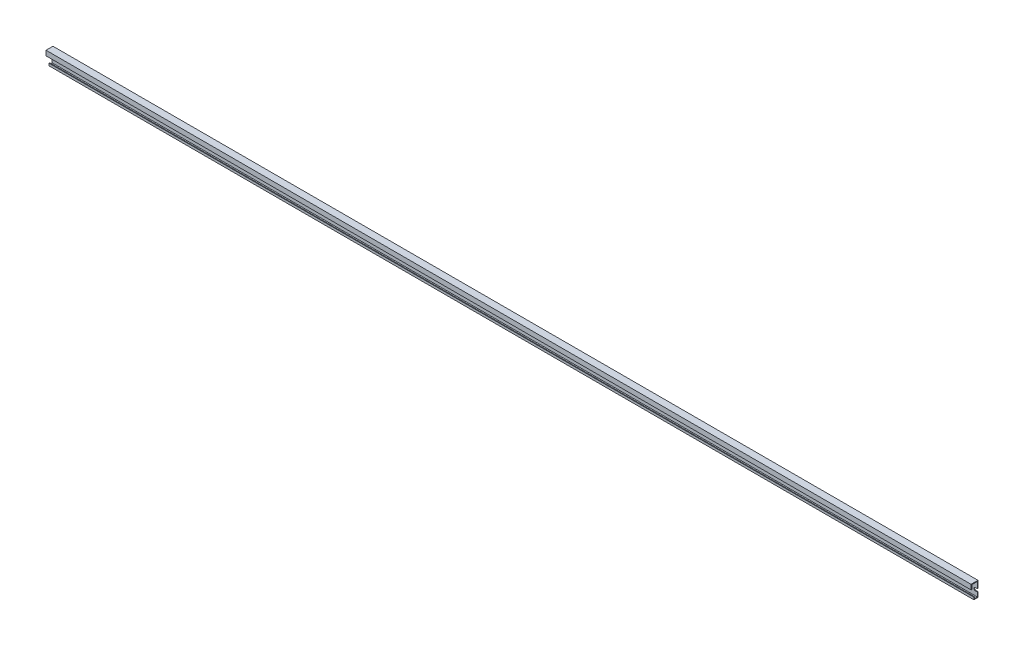
SolidWorks part; units mm, degrees
ref_plane "Front Plane" through (0, 0, 0) normal (0, 0, 1) x (1, 0, 0)
ref_plane "Top Plane" through (0, 0, 0) normal (0, 1, 0) x (1, 0, 0)
ref_plane "Right Plane" through (0, 0, 0) normal (1, 0, 0) x (0, 0, -1)
ref_plane "Plane1" through (0, -11, 0) normal (0, 1, 0) x (1, 0, 0)
sketch "Sketch1" plane through (0, -11, 0) normal (0, 1, 0) x (1, 0, 0)
  line L0 (2000, -9) -> (2000, 0)
  line L1 (2000, 0) -> (0, 0)
  line L2 (0, 0) -> (0, -9)
  line L3 (0, -9) -> (2000, -9)
extrude "Boss-Extrude1" add sketch "Sketch1" against normal blind 5
sketch "Sketch2" plane through (0, 0, 0) normal (-1, 0, 0) x (0, 0, 1)
  line L0 (0, -14.5) -> (7.5, -14.5)
  line L1 (7.5, -14.5) -> (7.5, -11)
  line L2 (7.5, -11) -> (0, -11)
  line L3 (0, -11) -> (0, -14.5)
extrude "Cut-Extrude1" cut sketch "Sketch2" against normal through all
sketch "Sketch3" plane through (0, -14.5, 0) normal (0, 1, 0) x (-1, 0, 0)
  line L0 (0, 1.5) -> (0, 0)
  line L1 (0, 0) -> (-2000, 0)
  line L2 (-2000, 0) -> (-2000, 1.5)
  line L3 (-2000, 1.5) -> (0, 1.5)
extrude "Boss-Extrude2" add sketch "Sketch3" along normal blind 30.5
sketch "Sketch4" plane through (0, 0, 1.5) normal (0, 0, 1) x (1, 0, 0)
  line L0 (0, 14.5) -> (0, 16)
  line L1 (0, 16) -> (2000, 16)
  line L2 (2000, 16) -> (2000, 14.5)
  line L3 (2000, 14.5) -> (0, 14.5)
extrude "Boss-Extrude3" add sketch "Sketch4" along normal blind 13.5
sketch "Sketch5" plane through (0, 14.5, 0) normal (0, -1, 0) x (1, 0, 0)
  line L0 (2000, 15) -> (2000, 13.5)
  line L1 (2000, 13.5) -> (0, 13.5)
  line L2 (0, 13.5) -> (0, 15)
  line L3 (0, 15) -> (2000, 15)
extrude "Boss-Extrude4" add sketch "Sketch5" along normal blind 9
sketch "Sketch6" plane through (0, 0, 0) normal (0, 0, -1) x (-1, 0, 0)
  line L0 (0, -5.1) -> (0, 1.1)
  line L1 (0, 1.1) -> (-4.4, 1.1)
  line L2 (-4.4, -5.1) -> (0, -5.1)
  arc A0 (-4.4, 1.1) -> (-4.4, -5.1) centre (-4.4, -2) ccw
extrude "Cut-Extrude2" cut sketch "Sketch6" against normal through all
sketch "Sketch7" plane through (0, 0, 0) normal (0, 0, -1) x (-1, 0, 0)
  line L0 (-2000, 1.1) -> (-2000, -5.1)
  line L1 (-2000, -5.1) -> (-1995.6, -5.1)
  line L2 (-1995.6, 1.1) -> (-2000, 1.1)
  arc A0 (-1995.6, -5.1) -> (-1995.6, 1.1) centre (-1995.6, -2) ccw
extrude "Cut-Extrude3" cut sketch "Sketch7" against normal through all
sketch "Sketch8" plane through (0, 0, 1.5) normal (0, 0, 1) x (1, 0, 0)
  line L0 (1229.4, 1.1) -> (1220.6, 1.1)
  line L1 (1220.6, -5.1) -> (1229.4, -5.1)
  arc A0 (1220.6, 1.1) -> (1220.6, -5.1) centre (1220.6, -2) ccw
  arc A1 (1229.4, -5.1) -> (1229.4, 1.1) centre (1229.4, -2) ccw
extrude "Cut-Extrude4" cut sketch "Sketch8" against normal through all
sketch "Sketch9" plane through (0, 0, 1.5) normal (0, 0, 1) x (1, 0, 0)
  line L0 (279.4, 1.1) -> (270.6, 1.1)
  line L1 (270.6, -5.1) -> (279.4, -5.1)
  arc A0 (270.6, 1.1) -> (270.6, -5.1) centre (270.6, -2) ccw
  arc A1 (279.4, -5.1) -> (279.4, 1.1) centre (279.4, -2) ccw
extrude "Cut-Extrude5" cut sketch "Sketch9" against normal through all
sketch "Sketch10" plane through (0, 0, 1.5) normal (0, 0, 1) x (1, 0, 0)
  line L0 (1404.4, 1.1) -> (1395.6, 1.1)
  line L1 (1395.6, -5.1) -> (1404.4, -5.1)
  arc A0 (1395.6, 1.1) -> (1395.6, -5.1) centre (1395.6, -2) ccw
  arc A1 (1404.4, -5.1) -> (1404.4, 1.1) centre (1404.4, -2) ccw
extrude "Cut-Extrude6" cut sketch "Sketch10" against normal through all
sketch "Sketch11" plane through (0, 0, 1.5) normal (0, 0, 1) x (1, 0, 0)
  line L0 (1729.4, 1.1) -> (1720.6, 1.1)
  line L1 (1720.6, -5.1) -> (1729.4, -5.1)
  arc A0 (1729.4, -5.1) -> (1729.4, 1.1) centre (1729.4, -2) ccw
  arc A1 (1720.6, 1.1) -> (1720.6, -5.1) centre (1720.6, -2) ccw
extrude "Cut-Extrude7" cut sketch "Sketch11" against normal through all
sketch "Sketch12" plane through (0, 0, 1.5) normal (0, 0, 1) x (1, 0, 0)
  line L0 (1954.4, 1.1) -> (1945.6, 1.1)
  line L1 (1945.6, -5.1) -> (1954.4, -5.1)
  arc A0 (1954.4, -5.1) -> (1954.4, 1.1) centre (1954.4, -2) ccw
  arc A1 (1945.6, 1.1) -> (1945.6, -5.1) centre (1945.6, -2) ccw
extrude "Cut-Extrude8" cut sketch "Sketch12" against normal through all
sketch "Sketch13" plane through (0, 0, 1.5) normal (0, 0, 1) x (1, 0, 0)
  line L0 (679.4, 1.1) -> (670.6, 1.1)
  line L1 (670.6, -5.1) -> (679.4, -5.1)
  arc A0 (670.6, 1.1) -> (670.6, -5.1) centre (670.6, -2) ccw
  arc A1 (679.4, -5.1) -> (679.4, 1.1) centre (679.4, -2) ccw
extrude "Cut-Extrude9" cut sketch "Sketch13" against normal through all
sketch "Sketch14" plane through (0, 0, 1.5) normal (0, 0, 1) x (1, 0, 0)
  line L0 (29.4, 1.1) -> (20.6, 1.1)
  line L1 (20.6, -5.1) -> (29.4, -5.1)
  arc A0 (20.6, 1.1) -> (20.6, -5.1) centre (20.6, -2) ccw
  arc A1 (29.4, -5.1) -> (29.4, 1.1) centre (29.4, -2) ccw
extrude "Cut-Extrude10" cut sketch "Sketch14" against normal through all
sketch "Sketch15" plane through (0, 0, 1.5) normal (0, 0, 1) x (1, 0, 0)
  line L0 (1979.4, 1.1) -> (1970.6, 1.1)
  line L1 (1970.6, -5.1) -> (1979.4, -5.1)
  arc A0 (1979.4, -5.1) -> (1979.4, 1.1) centre (1979.4, -2) ccw
  arc A1 (1970.6, 1.1) -> (1970.6, -5.1) centre (1970.6, -2) ccw
extrude "Cut-Extrude11" cut sketch "Sketch15" against normal through all
sketch "Sketch16" plane through (0, 0, 1.5) normal (0, 0, 1) x (1, 0, 0)
  line L0 (104.4, 1.1) -> (95.6, 1.1)
  line L1 (95.6, -5.1) -> (104.4, -5.1)
  arc A0 (95.6, 1.1) -> (95.6, -5.1) centre (95.6, -2) ccw
  arc A1 (104.4, -5.1) -> (104.4, 1.1) centre (104.4, -2) ccw
extrude "Cut-Extrude12" cut sketch "Sketch16" against normal through all
sketch "Sketch17" plane through (0, 0, 1.5) normal (0, 0, 1) x (1, 0, 0)
  line L0 (1479.4, 1.1) -> (1470.6, 1.1)
  line L1 (1470.6, -5.1) -> (1479.4, -5.1)
  arc A0 (1479.4, -5.1) -> (1479.4, 1.1) centre (1479.4, -2) ccw
  arc A1 (1470.6, 1.1) -> (1470.6, -5.1) centre (1470.6, -2) ccw
extrude "Cut-Extrude13" cut sketch "Sketch17" against normal through all
sketch "Sketch18" plane through (0, 0, 1.5) normal (0, 0, 1) x (1, 0, 0)
  line L0 (295.6, -5.1) -> (304.4, -5.1)
  line L1 (304.4, 1.1) -> (295.6, 1.1)
  arc A0 (304.4, -5.1) -> (304.4, 1.1) centre (304.4, -2) ccw
  arc A1 (295.6, 1.1) -> (295.6, -5.1) centre (295.6, -2) ccw
extrude "Cut-Extrude14" cut sketch "Sketch18" against normal through all
sketch "Sketch19" plane through (0, 0, 1.5) normal (0, 0, 1) x (1, 0, 0)
  line L0 (170.6, -5.1) -> (179.4, -5.1)
  line L1 (179.4, 1.1) -> (170.6, 1.1)
  arc A0 (179.4, -5.1) -> (179.4, 1.1) centre (179.4, -2) ccw
  arc A1 (170.6, 1.1) -> (170.6, -5.1) centre (170.6, -2) ccw
extrude "Cut-Extrude15" cut sketch "Sketch19" against normal through all
sketch "Sketch20" plane through (0, 0, 1.5) normal (0, 0, 1) x (1, 0, 0)
  line L0 (1320.6, -5.1) -> (1329.4, -5.1)
  line L1 (1329.4, 1.1) -> (1320.6, 1.1)
  arc A0 (1329.4, -5.1) -> (1329.4, 1.1) centre (1329.4, -2) ccw
  arc A1 (1320.6, 1.1) -> (1320.6, -5.1) centre (1320.6, -2) ccw
extrude "Cut-Extrude16" cut sketch "Sketch20" against normal through all
sketch "Sketch21" plane through (0, 0, 1.5) normal (0, 0, 1) x (1, 0, 0)
  line L0 (704.4, 1.1) -> (695.6, 1.1)
  line L1 (695.6, -5.1) -> (704.4, -5.1)
  arc A0 (695.6, 1.1) -> (695.6, -5.1) centre (695.6, -2) ccw
  arc A1 (704.4, -5.1) -> (704.4, 1.1) centre (704.4, -2) ccw
extrude "Cut-Extrude17" cut sketch "Sketch21" against normal through all
sketch "Sketch22" plane through (0, 0, 1.5) normal (0, 0, 1) x (1, 0, 0)
  line L0 (379.4, 1.1) -> (370.6, 1.1)
  line L1 (370.6, -5.1) -> (379.4, -5.1)
  arc A0 (370.6, 1.1) -> (370.6, -5.1) centre (370.6, -2) ccw
  arc A1 (379.4, -5.1) -> (379.4, 1.1) centre (379.4, -2) ccw
extrude "Cut-Extrude18" cut sketch "Sketch22" against normal through all
sketch "Sketch23" plane through (0, 0, 1.5) normal (0, 0, 1) x (1, 0, 0)
  line L0 (1554.4, 1.1) -> (1545.6, 1.1)
  line L1 (1545.6, -5.1) -> (1554.4, -5.1)
  arc A0 (1554.4, -5.1) -> (1554.4, 1.1) centre (1554.4, -2) ccw
  arc A1 (1545.6, 1.1) -> (1545.6, -5.1) centre (1545.6, -2) ccw
extrude "Cut-Extrude19" cut sketch "Sketch23" against normal through all
sketch "Sketch24" plane through (0, 0, 1.5) normal (0, 0, 1) x (1, 0, 0)
  line L0 (1704.4, 1.1) -> (1695.6, 1.1)
  line L1 (1695.6, -5.1) -> (1704.4, -5.1)
  arc A0 (1695.6, 1.1) -> (1695.6, -5.1) centre (1695.6, -2) ccw
  arc A1 (1704.4, -5.1) -> (1704.4, 1.1) centre (1704.4, -2) ccw
extrude "Cut-Extrude20" cut sketch "Sketch24" against normal through all
sketch "Sketch25" plane through (0, 0, 1.5) normal (0, 0, 1) x (1, 0, 0)
  line L0 (1004.4, 1.1) -> (995.6, 1.1)
  line L1 (995.6, -5.1) -> (1004.4, -5.1)
  arc A0 (995.6, 1.1) -> (995.6, -5.1) centre (995.6, -2) ccw
  arc A1 (1004.4, -5.1) -> (1004.4, 1.1) centre (1004.4, -2) ccw
extrude "Cut-Extrude21" cut sketch "Sketch25" against normal through all
sketch "Sketch26" plane through (0, 0, 1.5) normal (0, 0, 1) x (1, 0, 0)
  line L0 (545.6, -5.1) -> (554.4, -5.1)
  line L1 (554.4, 1.1) -> (545.6, 1.1)
  arc A0 (554.4, -5.1) -> (554.4, 1.1) centre (554.4, -2) ccw
  arc A1 (545.6, 1.1) -> (545.6, -5.1) centre (545.6, -2) ccw
extrude "Cut-Extrude22" cut sketch "Sketch26" against normal through all
sketch "Sketch27" plane through (0, 0, 1.5) normal (0, 0, 1) x (1, 0, 0)
  line L0 (845.6, -5.1) -> (854.4, -5.1)
  line L1 (854.4, 1.1) -> (845.6, 1.1)
  arc A0 (854.4, -5.1) -> (854.4, 1.1) centre (854.4, -2) ccw
  arc A1 (845.6, 1.1) -> (845.6, -5.1) centre (845.6, -2) ccw
extrude "Cut-Extrude23" cut sketch "Sketch27" against normal through all
sketch "Sketch28" plane through (0, 0, 1.5) normal (0, 0, 1) x (1, 0, 0)
  line L0 (879.4, 1.1) -> (870.6, 1.1)
  line L1 (870.6, -5.1) -> (879.4, -5.1)
  arc A0 (870.6, 1.1) -> (870.6, -5.1) centre (870.6, -2) ccw
  arc A1 (879.4, -5.1) -> (879.4, 1.1) centre (879.4, -2) ccw
extrude "Cut-Extrude24" cut sketch "Sketch28" against normal through all
sketch "Sketch29" plane through (0, 0, 1.5) normal (0, 0, 1) x (1, 0, 0)
  line L0 (354.4, 1.1) -> (345.6, 1.1)
  line L1 (345.6, -5.1) -> (354.4, -5.1)
  arc A0 (345.6, 1.1) -> (345.6, -5.1) centre (345.6, -2) ccw
  arc A1 (354.4, -5.1) -> (354.4, 1.1) centre (354.4, -2) ccw
extrude "Cut-Extrude25" cut sketch "Sketch29" against normal through all
sketch "Sketch30" plane through (0, 0, 1.5) normal (0, 0, 1) x (1, 0, 0)
  line L0 (1679.4, 1.1) -> (1670.6, 1.1)
  line L1 (1670.6, -5.1) -> (1679.4, -5.1)
  arc A0 (1670.6, 1.1) -> (1670.6, -5.1) centre (1670.6, -2) ccw
  arc A1 (1679.4, -5.1) -> (1679.4, 1.1) centre (1679.4, -2) ccw
extrude "Cut-Extrude26" cut sketch "Sketch30" against normal through all
sketch "Sketch31" plane through (0, 0, 1.5) normal (0, 0, 1) x (1, 0, 0)
  line L0 (395.6, -5.1) -> (404.4, -5.1)
  line L1 (404.4, 1.1) -> (395.6, 1.1)
  arc A0 (404.4, -5.1) -> (404.4, 1.1) centre (404.4, -2) ccw
  arc A1 (395.6, 1.1) -> (395.6, -5.1) centre (395.6, -2) ccw
extrude "Cut-Extrude27" cut sketch "Sketch31" against normal through all
sketch "Sketch32" plane through (0, 0, 1.5) normal (0, 0, 1) x (1, 0, 0)
  line L0 (1454.4, 1.1) -> (1445.6, 1.1)
  line L1 (1445.6, -5.1) -> (1454.4, -5.1)
  arc A0 (1445.6, 1.1) -> (1445.6, -5.1) centre (1445.6, -2) ccw
  arc A1 (1454.4, -5.1) -> (1454.4, 1.1) centre (1454.4, -2) ccw
extrude "Cut-Extrude28" cut sketch "Sketch32" against normal through all
sketch "Sketch33" plane through (0, 0, 1.5) normal (0, 0, 1) x (1, 0, 0)
  line L0 (54.4, 1.1) -> (45.6, 1.1)
  line L1 (45.6, -5.1) -> (54.4, -5.1)
  arc A0 (45.6, 1.1) -> (45.6, -5.1) centre (45.6, -2) ccw
  arc A1 (54.4, -5.1) -> (54.4, 1.1) centre (54.4, -2) ccw
extrude "Cut-Extrude29" cut sketch "Sketch33" against normal through all
sketch "Sketch34" plane through (0, 0, 1.5) normal (0, 0, 1) x (1, 0, 0)
  line L0 (1604.4, 1.1) -> (1595.6, 1.1)
  line L1 (1595.6, -5.1) -> (1604.4, -5.1)
  arc A0 (1595.6, 1.1) -> (1595.6, -5.1) centre (1595.6, -2) ccw
  arc A1 (1604.4, -5.1) -> (1604.4, 1.1) centre (1604.4, -2) ccw
extrude "Cut-Extrude30" cut sketch "Sketch34" against normal through all
sketch "Sketch35" plane through (0, 0, 1.5) normal (0, 0, 1) x (1, 0, 0)
  line L0 (1929.4, 1.1) -> (1920.6, 1.1)
  line L1 (1920.6, -5.1) -> (1929.4, -5.1)
  arc A0 (1920.6, 1.1) -> (1920.6, -5.1) centre (1920.6, -2) ccw
  arc A1 (1929.4, -5.1) -> (1929.4, 1.1) centre (1929.4, -2) ccw
extrude "Cut-Extrude31" cut sketch "Sketch35" against normal through all
sketch "Sketch36" plane through (0, 0, 1.5) normal (0, 0, 1) x (1, 0, 0)
  line L0 (570.6, -5.1) -> (579.4, -5.1)
  line L1 (579.4, 1.1) -> (570.6, 1.1)
  arc A0 (579.4, -5.1) -> (579.4, 1.1) centre (579.4, -2) ccw
  arc A1 (570.6, 1.1) -> (570.6, -5.1) centre (570.6, -2) ccw
extrude "Cut-Extrude32" cut sketch "Sketch36" against normal through all
sketch "Sketch37" plane through (0, 0, 1.5) normal (0, 0, 1) x (1, 0, 0)
  line L0 (979.4, 1.1) -> (970.6, 1.1)
  line L1 (970.6, -5.1) -> (979.4, -5.1)
  arc A0 (970.6, 1.1) -> (970.6, -5.1) centre (970.6, -2) ccw
  arc A1 (979.4, -5.1) -> (979.4, 1.1) centre (979.4, -2) ccw
extrude "Cut-Extrude33" cut sketch "Sketch37" against normal through all
sketch "Sketch38" plane through (0, 0, 1.5) normal (0, 0, 1) x (1, 0, 0)
  line L0 (1629.4, 1.1) -> (1620.6, 1.1)
  line L1 (1620.6, -5.1) -> (1629.4, -5.1)
  arc A0 (1629.4, -5.1) -> (1629.4, 1.1) centre (1629.4, -2) ccw
  arc A1 (1620.6, 1.1) -> (1620.6, -5.1) centre (1620.6, -2) ccw
extrude "Cut-Extrude34" cut sketch "Sketch38" against normal through all
sketch "Sketch39" plane through (0, 0, 1.5) normal (0, 0, 1) x (1, 0, 0)
  line L0 (145.6, -5.1) -> (154.4, -5.1)
  line L1 (154.4, 1.1) -> (145.6, 1.1)
  arc A0 (154.4, -5.1) -> (154.4, 1.1) centre (154.4, -2) ccw
  arc A1 (145.6, 1.1) -> (145.6, -5.1) centre (145.6, -2) ccw
extrude "Cut-Extrude35" cut sketch "Sketch39" against normal through all
sketch "Sketch40" plane through (0, 0, 1.5) normal (0, 0, 1) x (1, 0, 0)
  line L0 (1304.4, 1.1) -> (1295.6, 1.1)
  line L1 (1295.6, -5.1) -> (1304.4, -5.1)
  arc A0 (1304.4, -5.1) -> (1304.4, 1.1) centre (1304.4, -2) ccw
  arc A1 (1295.6, 1.1) -> (1295.6, -5.1) centre (1295.6, -2) ccw
extrude "Cut-Extrude36" cut sketch "Sketch40" against normal through all
sketch "Sketch41" plane through (0, 0, 1.5) normal (0, 0, 1) x (1, 0, 0)
  line L0 (1854.4, 1.1) -> (1845.6, 1.1)
  line L1 (1845.6, -5.1) -> (1854.4, -5.1)
  arc A0 (1854.4, -5.1) -> (1854.4, 1.1) centre (1854.4, -2) ccw
  arc A1 (1845.6, 1.1) -> (1845.6, -5.1) centre (1845.6, -2) ccw
extrude "Cut-Extrude37" cut sketch "Sketch41" against normal through all
sketch "Sketch42" plane through (0, 0, 1.5) normal (0, 0, 1) x (1, 0, 0)
  line L0 (1879.4, 1.1) -> (1870.6, 1.1)
  line L1 (1870.6, -5.1) -> (1879.4, -5.1)
  arc A0 (1879.4, -5.1) -> (1879.4, 1.1) centre (1879.4, -2) ccw
  arc A1 (1870.6, 1.1) -> (1870.6, -5.1) centre (1870.6, -2) ccw
extrude "Cut-Extrude38" cut sketch "Sketch42" against normal through all
sketch "Sketch43" plane through (0, 0, 1.5) normal (0, 0, 1) x (1, 0, 0)
  line L0 (729.4, 1.1) -> (720.6, 1.1)
  line L1 (720.6, -5.1) -> (729.4, -5.1)
  arc A0 (720.6, 1.1) -> (720.6, -5.1) centre (720.6, -2) ccw
  arc A1 (729.4, -5.1) -> (729.4, 1.1) centre (729.4, -2) ccw
extrude "Cut-Extrude39" cut sketch "Sketch43" against normal through all
sketch "Sketch44" plane through (0, 0, 1.5) normal (0, 0, 1) x (1, 0, 0)
  line L0 (1504.4, 1.1) -> (1495.6, 1.1)
  line L1 (1495.6, -5.1) -> (1504.4, -5.1)
  arc A0 (1495.6, 1.1) -> (1495.6, -5.1) centre (1495.6, -2) ccw
  arc A1 (1504.4, -5.1) -> (1504.4, 1.1) centre (1504.4, -2) ccw
extrude "Cut-Extrude40" cut sketch "Sketch44" against normal through all
sketch "Sketch45" plane through (0, 0, 1.5) normal (0, 0, 1) x (1, 0, 0)
  line L0 (1420.6, -5.1) -> (1429.4, -5.1)
  line L1 (1429.4, 1.1) -> (1420.6, 1.1)
  arc A0 (1429.4, -5.1) -> (1429.4, 1.1) centre (1429.4, -2) ccw
  arc A1 (1420.6, 1.1) -> (1420.6, -5.1) centre (1420.6, -2) ccw
extrude "Cut-Extrude41" cut sketch "Sketch45" against normal through all
sketch "Sketch46" plane through (0, 0, 1.5) normal (0, 0, 1) x (1, 0, 0)
  line L0 (629.4, 1.1) -> (620.6, 1.1)
  line L1 (620.6, -5.1) -> (629.4, -5.1)
  arc A0 (620.6, 1.1) -> (620.6, -5.1) centre (620.6, -2) ccw
  arc A1 (629.4, -5.1) -> (629.4, 1.1) centre (629.4, -2) ccw
extrude "Cut-Extrude42" cut sketch "Sketch46" against normal through all
sketch "Sketch47" plane through (0, 0, 1.5) normal (0, 0, 1) x (1, 0, 0)
  line L0 (1270.6, -5.1) -> (1279.4, -5.1)
  line L1 (1279.4, 1.1) -> (1270.6, 1.1)
  arc A0 (1279.4, -5.1) -> (1279.4, 1.1) centre (1279.4, -2) ccw
  arc A1 (1270.6, 1.1) -> (1270.6, -5.1) centre (1270.6, -2) ccw
extrude "Cut-Extrude43" cut sketch "Sketch47" against normal through all
sketch "Sketch48" plane through (0, 0, 1.5) normal (0, 0, 1) x (1, 0, 0)
  line L0 (1379.4, 1.1) -> (1370.6, 1.1)
  line L1 (1370.6, -5.1) -> (1379.4, -5.1)
  arc A0 (1379.4, -5.1) -> (1379.4, 1.1) centre (1379.4, -2) ccw
  arc A1 (1370.6, 1.1) -> (1370.6, -5.1) centre (1370.6, -2) ccw
extrude "Cut-Extrude44" cut sketch "Sketch48" against normal through all
sketch "Sketch49" plane through (0, 0, 1.5) normal (0, 0, 1) x (1, 0, 0)
  line L0 (1529.4, 1.1) -> (1520.6, 1.1)
  line L1 (1520.6, -5.1) -> (1529.4, -5.1)
  arc A0 (1520.6, 1.1) -> (1520.6, -5.1) centre (1520.6, -2) ccw
  arc A1 (1529.4, -5.1) -> (1529.4, 1.1) centre (1529.4, -2) ccw
extrude "Cut-Extrude45" cut sketch "Sketch49" against normal through all
sketch "Sketch50" plane through (0, 0, 1.5) normal (0, 0, 1) x (1, 0, 0)
  line L0 (920.6, -5.1) -> (929.4, -5.1)
  line L1 (929.4, 1.1) -> (920.6, 1.1)
  arc A0 (929.4, -5.1) -> (929.4, 1.1) centre (929.4, -2) ccw
  arc A1 (920.6, 1.1) -> (920.6, -5.1) centre (920.6, -2) ccw
extrude "Cut-Extrude46" cut sketch "Sketch50" against normal through all
sketch "Sketch51" plane through (0, 0, 1.5) normal (0, 0, 1) x (1, 0, 0)
  line L0 (1154.4, 1.1) -> (1145.6, 1.1)
  line L1 (1145.6, -5.1) -> (1154.4, -5.1)
  arc A0 (1145.6, 1.1) -> (1145.6, -5.1) centre (1145.6, -2) ccw
  arc A1 (1154.4, -5.1) -> (1154.4, 1.1) centre (1154.4, -2) ccw
extrude "Cut-Extrude47" cut sketch "Sketch51" against normal through all
sketch "Sketch52" plane through (0, 0, 1.5) normal (0, 0, 1) x (1, 0, 0)
  line L0 (654.4, 1.1) -> (645.6, 1.1)
  line L1 (645.6, -5.1) -> (654.4, -5.1)
  arc A0 (654.4, -5.1) -> (654.4, 1.1) centre (654.4, -2) ccw
  arc A1 (645.6, 1.1) -> (645.6, -5.1) centre (645.6, -2) ccw
extrude "Cut-Extrude48" cut sketch "Sketch52" against normal through all
sketch "Sketch53" plane through (0, 0, 1.5) normal (0, 0, 1) x (1, 0, 0)
  line L0 (1254.4, 1.1) -> (1245.6, 1.1)
  line L1 (1245.6, -5.1) -> (1254.4, -5.1)
  arc A0 (1245.6, 1.1) -> (1245.6, -5.1) centre (1245.6, -2) ccw
  arc A1 (1254.4, -5.1) -> (1254.4, 1.1) centre (1254.4, -2) ccw
extrude "Cut-Extrude49" cut sketch "Sketch53" against normal through all
sketch "Sketch54" plane through (0, 0, 1.5) normal (0, 0, 1) x (1, 0, 0)
  line L0 (954.4, 1.1) -> (945.6, 1.1)
  line L1 (945.6, -5.1) -> (954.4, -5.1)
  arc A0 (945.6, 1.1) -> (945.6, -5.1) centre (945.6, -2) ccw
  arc A1 (954.4, -5.1) -> (954.4, 1.1) centre (954.4, -2) ccw
extrude "Cut-Extrude50" cut sketch "Sketch54" against normal through all
sketch "Sketch55" plane through (0, 0, 1.5) normal (0, 0, 1) x (1, 0, 0)
  line L0 (1104.4, 1.1) -> (1095.6, 1.1)
  line L1 (1095.6, -5.1) -> (1104.4, -5.1)
  arc A0 (1095.6, 1.1) -> (1095.6, -5.1) centre (1095.6, -2) ccw
  arc A1 (1104.4, -5.1) -> (1104.4, 1.1) centre (1104.4, -2) ccw
extrude "Cut-Extrude51" cut sketch "Sketch55" against normal through all
sketch "Sketch56" plane through (0, 0, 1.5) normal (0, 0, 1) x (1, 0, 0)
  line L0 (1079.4, 1.1) -> (1070.6, 1.1)
  line L1 (1070.6, -5.1) -> (1079.4, -5.1)
  arc A0 (1079.4, -5.1) -> (1079.4, 1.1) centre (1079.4, -2) ccw
  arc A1 (1070.6, 1.1) -> (1070.6, -5.1) centre (1070.6, -2) ccw
extrude "Cut-Extrude52" cut sketch "Sketch56" against normal through all
sketch "Sketch57" plane through (0, 0, 1.5) normal (0, 0, 1) x (1, 0, 0)
  line L0 (770.6, -5.1) -> (779.4, -5.1)
  line L1 (779.4, 1.1) -> (770.6, 1.1)
  arc A0 (779.4, -5.1) -> (779.4, 1.1) centre (779.4, -2) ccw
  arc A1 (770.6, 1.1) -> (770.6, -5.1) centre (770.6, -2) ccw
extrude "Cut-Extrude53" cut sketch "Sketch57" against normal through all
sketch "Sketch58" plane through (0, 0, 1.5) normal (0, 0, 1) x (1, 0, 0)
  line L0 (1179.4, 1.1) -> (1170.6, 1.1)
  line L1 (1170.6, -5.1) -> (1179.4, -5.1)
  arc A0 (1170.6, 1.1) -> (1170.6, -5.1) centre (1170.6, -2) ccw
  arc A1 (1179.4, -5.1) -> (1179.4, 1.1) centre (1179.4, -2) ccw
extrude "Cut-Extrude54" cut sketch "Sketch58" against normal through all
sketch "Sketch59" plane through (0, 0, 1.5) normal (0, 0, 1) x (1, 0, 0)
  line L0 (1579.4, 1.1) -> (1570.6, 1.1)
  line L1 (1570.6, -5.1) -> (1579.4, -5.1)
  arc A0 (1570.6, 1.1) -> (1570.6, -5.1) centre (1570.6, -2) ccw
  arc A1 (1579.4, -5.1) -> (1579.4, 1.1) centre (1579.4, -2) ccw
extrude "Cut-Extrude55" cut sketch "Sketch59" against normal through all
sketch "Sketch60" plane through (0, 0, 1.5) normal (0, 0, 1) x (1, 0, 0)
  line L0 (1054.4, 1.1) -> (1045.6, 1.1)
  line L1 (1045.6, -5.1) -> (1054.4, -5.1)
  arc A0 (1045.6, 1.1) -> (1045.6, -5.1) centre (1045.6, -2) ccw
  arc A1 (1054.4, -5.1) -> (1054.4, 1.1) centre (1054.4, -2) ccw
extrude "Cut-Extrude56" cut sketch "Sketch60" against normal through all
sketch "Sketch61" plane through (0, 0, 1.5) normal (0, 0, 1) x (1, 0, 0)
  line L0 (420.6, -5.1) -> (429.4, -5.1)
  line L1 (429.4, 1.1) -> (420.6, 1.1)
  arc A0 (429.4, -5.1) -> (429.4, 1.1) centre (429.4, -2) ccw
  arc A1 (420.6, 1.1) -> (420.6, -5.1) centre (420.6, -2) ccw
extrude "Cut-Extrude57" cut sketch "Sketch61" against normal through all
sketch "Sketch62" plane through (0, 0, 1.5) normal (0, 0, 1) x (1, 0, 0)
  line L0 (1654.4, 1.1) -> (1645.6, 1.1)
  line L1 (1645.6, -5.1) -> (1654.4, -5.1)
  arc A0 (1645.6, 1.1) -> (1645.6, -5.1) centre (1645.6, -2) ccw
  arc A1 (1654.4, -5.1) -> (1654.4, 1.1) centre (1654.4, -2) ccw
extrude "Cut-Extrude58" cut sketch "Sketch62" against normal through all
sketch "Sketch63" plane through (0, 0, 1.5) normal (0, 0, 1) x (1, 0, 0)
  line L0 (820.6, -5.1) -> (829.4, -5.1)
  line L1 (829.4, 1.1) -> (820.6, 1.1)
  arc A0 (829.4, -5.1) -> (829.4, 1.1) centre (829.4, -2) ccw
  arc A1 (820.6, 1.1) -> (820.6, -5.1) centre (820.6, -2) ccw
extrude "Cut-Extrude59" cut sketch "Sketch63" against normal through all
sketch "Sketch64" plane through (0, 0, 1.5) normal (0, 0, 1) x (1, 0, 0)
  line L0 (1829.4, 1.1) -> (1820.6, 1.1)
  line L1 (1820.6, -5.1) -> (1829.4, -5.1)
  arc A0 (1829.4, -5.1) -> (1829.4, 1.1) centre (1829.4, -2) ccw
  arc A1 (1820.6, 1.1) -> (1820.6, -5.1) centre (1820.6, -2) ccw
extrude "Cut-Extrude60" cut sketch "Sketch64" against normal through all
sketch "Sketch65" plane through (0, 0, 1.5) normal (0, 0, 1) x (1, 0, 0)
  line L0 (1904.4, 1.1) -> (1895.6, 1.1)
  line L1 (1895.6, -5.1) -> (1904.4, -5.1)
  arc A0 (1904.4, -5.1) -> (1904.4, 1.1) centre (1904.4, -2) ccw
  arc A1 (1895.6, 1.1) -> (1895.6, -5.1) centre (1895.6, -2) ccw
extrude "Cut-Extrude61" cut sketch "Sketch65" against normal through all
sketch "Sketch66" plane through (0, 0, 1.5) normal (0, 0, 1) x (1, 0, 0)
  line L0 (804.4, 1.1) -> (795.6, 1.1)
  line L1 (795.6, -5.1) -> (804.4, -5.1)
  arc A0 (795.6, 1.1) -> (795.6, -5.1) centre (795.6, -2) ccw
  arc A1 (804.4, -5.1) -> (804.4, 1.1) centre (804.4, -2) ccw
extrude "Cut-Extrude62" cut sketch "Sketch66" against normal through all
sketch "Sketch67" plane through (0, 0, 1.5) normal (0, 0, 1) x (1, 0, 0)
  line L0 (70.6, -5.1) -> (79.4, -5.1)
  line L1 (79.4, 1.1) -> (70.6, 1.1)
  arc A0 (79.4, -5.1) -> (79.4, 1.1) centre (79.4, -2) ccw
  arc A1 (70.6, 1.1) -> (70.6, -5.1) centre (70.6, -2) ccw
extrude "Cut-Extrude63" cut sketch "Sketch67" against normal through all
sketch "Sketch68" plane through (0, 0, 1.5) normal (0, 0, 1) x (1, 0, 0)
  line L0 (1204.4, 1.1) -> (1195.6, 1.1)
  line L1 (1195.6, -5.1) -> (1204.4, -5.1)
  arc A0 (1195.6, 1.1) -> (1195.6, -5.1) centre (1195.6, -2) ccw
  arc A1 (1204.4, -5.1) -> (1204.4, 1.1) centre (1204.4, -2) ccw
extrude "Cut-Extrude64" cut sketch "Sketch68" against normal through all
sketch "Sketch69" plane through (0, 0, 1.5) normal (0, 0, 1) x (1, 0, 0)
  line L0 (454.4, 1.1) -> (445.6, 1.1)
  line L1 (445.6, -5.1) -> (454.4, -5.1)
  arc A0 (445.6, 1.1) -> (445.6, -5.1) centre (445.6, -2) ccw
  arc A1 (454.4, -5.1) -> (454.4, 1.1) centre (454.4, -2) ccw
extrude "Cut-Extrude65" cut sketch "Sketch69" against normal through all
sketch "Sketch70" plane through (0, 0, 1.5) normal (0, 0, 1) x (1, 0, 0)
  line L0 (520.6, -5.1) -> (529.4, -5.1)
  line L1 (529.4, 1.1) -> (520.6, 1.1)
  arc A0 (529.4, -5.1) -> (529.4, 1.1) centre (529.4, -2) ccw
  arc A1 (520.6, 1.1) -> (520.6, -5.1) centre (520.6, -2) ccw
extrude "Cut-Extrude66" cut sketch "Sketch70" against normal through all
sketch "Sketch71" plane through (0, 0, 1.5) normal (0, 0, 1) x (1, 0, 0)
  line L0 (1129.4, 1.1) -> (1120.6, 1.1)
  line L1 (1120.6, -5.1) -> (1129.4, -5.1)
  arc A0 (1129.4, -5.1) -> (1129.4, 1.1) centre (1129.4, -2) ccw
  arc A1 (1120.6, 1.1) -> (1120.6, -5.1) centre (1120.6, -2) ccw
extrude "Cut-Extrude67" cut sketch "Sketch71" against normal through all
sketch "Sketch72" plane through (0, 0, 1.5) normal (0, 0, 1) x (1, 0, 0)
  line L0 (1029.4, 1.1) -> (1020.6, 1.1)
  line L1 (1020.6, -5.1) -> (1029.4, -5.1)
  arc A0 (1020.6, 1.1) -> (1020.6, -5.1) centre (1020.6, -2) ccw
  arc A1 (1029.4, -5.1) -> (1029.4, 1.1) centre (1029.4, -2) ccw
extrude "Cut-Extrude68" cut sketch "Sketch72" against normal through all
sketch "Sketch73" plane through (0, 0, 1.5) normal (0, 0, 1) x (1, 0, 0)
  line L0 (229.4, 1.1) -> (220.6, 1.1)
  line L1 (220.6, -5.1) -> (229.4, -5.1)
  arc A0 (229.4, -5.1) -> (229.4, 1.1) centre (229.4, -2) ccw
  arc A1 (220.6, 1.1) -> (220.6, -5.1) centre (220.6, -2) ccw
extrude "Cut-Extrude69" cut sketch "Sketch73" against normal through all
sketch "Sketch74" plane through (0, 0, 1.5) normal (0, 0, 1) x (1, 0, 0)
  line L0 (254.4, 1.1) -> (245.6, 1.1)
  line L1 (245.6, -5.1) -> (254.4, -5.1)
  arc A0 (245.6, 1.1) -> (245.6, -5.1) centre (245.6, -2) ccw
  arc A1 (254.4, -5.1) -> (254.4, 1.1) centre (254.4, -2) ccw
extrude "Cut-Extrude70" cut sketch "Sketch74" against normal through all
sketch "Sketch75" plane through (0, 0, 1.5) normal (0, 0, 1) x (1, 0, 0)
  line L0 (495.6, -5.1) -> (504.4, -5.1)
  line L1 (504.4, 1.1) -> (495.6, 1.1)
  arc A0 (504.4, -5.1) -> (504.4, 1.1) centre (504.4, -2) ccw
  arc A1 (495.6, 1.1) -> (495.6, -5.1) centre (495.6, -2) ccw
extrude "Cut-Extrude71" cut sketch "Sketch75" against normal through all
sketch "Sketch76" plane through (0, 0, 1.5) normal (0, 0, 1) x (1, 0, 0)
  line L0 (904.4, 1.1) -> (895.6, 1.1)
  line L1 (895.6, -5.1) -> (904.4, -5.1)
  arc A0 (895.6, 1.1) -> (895.6, -5.1) centre (895.6, -2) ccw
  arc A1 (904.4, -5.1) -> (904.4, 1.1) centre (904.4, -2) ccw
extrude "Cut-Extrude72" cut sketch "Sketch76" against normal through all
sketch "Sketch77" plane through (0, 0, 1.5) normal (0, 0, 1) x (1, 0, 0)
  line L0 (1754.4, 1.1) -> (1745.6, 1.1)
  line L1 (1745.6, -5.1) -> (1754.4, -5.1)
  arc A0 (1754.4, -5.1) -> (1754.4, 1.1) centre (1754.4, -2) ccw
  arc A1 (1745.6, 1.1) -> (1745.6, -5.1) centre (1745.6, -2) ccw
extrude "Cut-Extrude73" cut sketch "Sketch77" against normal through all
sketch "Sketch78" plane through (0, 0, 1.5) normal (0, 0, 1) x (1, 0, 0)
  line L0 (745.6, -5.1) -> (754.4, -5.1)
  line L1 (754.4, 1.1) -> (745.6, 1.1)
  arc A0 (754.4, -5.1) -> (754.4, 1.1) centre (754.4, -2) ccw
  arc A1 (745.6, 1.1) -> (745.6, -5.1) centre (745.6, -2) ccw
extrude "Cut-Extrude74" cut sketch "Sketch78" against normal through all
sketch "Sketch79" plane through (0, 0, 1.5) normal (0, 0, 1) x (1, 0, 0)
  line L0 (1354.4, 1.1) -> (1345.6, 1.1)
  line L1 (1345.6, -5.1) -> (1354.4, -5.1)
  arc A0 (1345.6, 1.1) -> (1345.6, -5.1) centre (1345.6, -2) ccw
  arc A1 (1354.4, -5.1) -> (1354.4, 1.1) centre (1354.4, -2) ccw
extrude "Cut-Extrude75" cut sketch "Sketch79" against normal through all
sketch "Sketch80" plane through (0, 0, 1.5) normal (0, 0, 1) x (1, 0, 0)
  line L0 (129.4, 1.1) -> (120.6, 1.1)
  line L1 (120.6, -5.1) -> (129.4, -5.1)
  arc A0 (120.6, 1.1) -> (120.6, -5.1) centre (120.6, -2) ccw
  arc A1 (129.4, -5.1) -> (129.4, 1.1) centre (129.4, -2) ccw
extrude "Cut-Extrude76" cut sketch "Sketch80" against normal through all
sketch "Sketch81" plane through (0, 0, 1.5) normal (0, 0, 1) x (1, 0, 0)
  line L0 (1779.4, 1.1) -> (1770.6, 1.1)
  line L1 (1770.6, -5.1) -> (1779.4, -5.1)
  arc A0 (1779.4, -5.1) -> (1779.4, 1.1) centre (1779.4, -2) ccw
  arc A1 (1770.6, 1.1) -> (1770.6, -5.1) centre (1770.6, -2) ccw
extrude "Cut-Extrude77" cut sketch "Sketch81" against normal through all
sketch "Sketch82" plane through (0, 0, 1.5) normal (0, 0, 1) x (1, 0, 0)
  line L0 (329.4, 1.1) -> (320.6, 1.1)
  line L1 (320.6, -5.1) -> (329.4, -5.1)
  arc A0 (320.6, 1.1) -> (320.6, -5.1) centre (320.6, -2) ccw
  arc A1 (329.4, -5.1) -> (329.4, 1.1) centre (329.4, -2) ccw
extrude "Cut-Extrude78" cut sketch "Sketch82" against normal through all
sketch "Sketch83" plane through (0, 0, 1.5) normal (0, 0, 1) x (1, 0, 0)
  line L0 (470.6, -5.1) -> (479.4, -5.1)
  line L1 (479.4, 1.1) -> (470.6, 1.1)
  arc A0 (479.4, -5.1) -> (479.4, 1.1) centre (479.4, -2) ccw
  arc A1 (470.6, 1.1) -> (470.6, -5.1) centre (470.6, -2) ccw
extrude "Cut-Extrude79" cut sketch "Sketch83" against normal through all
sketch "Sketch84" plane through (0, 0, 1.5) normal (0, 0, 1) x (1, 0, 0)
  line L0 (204.4, 1.1) -> (195.6, 1.1)
  line L1 (195.6, -5.1) -> (204.4, -5.1)
  arc A0 (195.6, 1.1) -> (195.6, -5.1) centre (195.6, -2) ccw
  arc A1 (204.4, -5.1) -> (204.4, 1.1) centre (204.4, -2) ccw
extrude "Cut-Extrude80" cut sketch "Sketch84" against normal through all
sketch "Sketch85" plane through (0, 0, 1.5) normal (0, 0, 1) x (1, 0, 0)
  line L0 (604.4, 1.1) -> (595.6, 1.1)
  line L1 (595.6, -5.1) -> (604.4, -5.1)
  arc A0 (595.6, 1.1) -> (595.6, -5.1) centre (595.6, -2) ccw
  arc A1 (604.4, -5.1) -> (604.4, 1.1) centre (604.4, -2) ccw
extrude "Cut-Extrude81" cut sketch "Sketch85" against normal through all
sketch "Sketch86" plane through (0, 0, 0) normal (0, 0, -1) x (-1, 0, 0)
  line L0 (-1804.4, -5.1) -> (-1795.6, -5.1)
  line L1 (-1795.6, 1.1) -> (-1804.4, 1.1)
  arc A0 (-1804.4, 1.1) -> (-1804.4, -5.1) centre (-1804.4, -2) ccw
  arc A1 (-1795.6, -5.1) -> (-1795.6, 1.1) centre (-1795.6, -2) ccw
extrude "Cut-Extrude82" cut sketch "Sketch86" against normal through all
